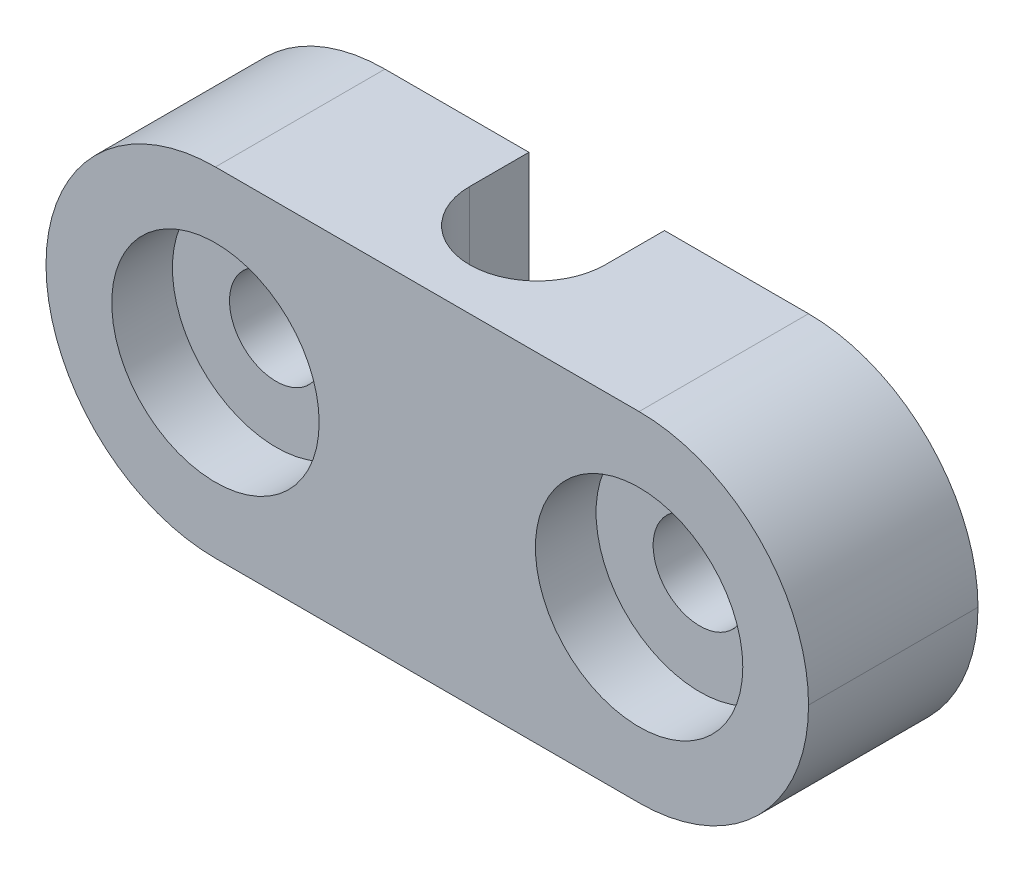
SolidWorks part; units mm, degrees
material "Plain Carbon Steel"
ref_plane "Front Plane" through (0, 0, 0) normal (0, 0, 1) x (1, 0, 0)
ref_plane "Top Plane" through (0, 0, 0) normal (0, 1, 0) x (1, 0, 0)
ref_plane "Right Plane" through (0, 0, 0) normal (1, 0, 0) x (0, 0, -1)
sketch "Sketch2" plane through (0, 0, 0) normal (0, 0, 1) x (1, 0, 0)
  line L1 (-22.5, -10) -> (22.5, -10)
  line L2 (-22.5, -10) -> (-22.5, 10)
  line L3 (-22.5, 10) -> (22.5, 10)
  line L4 (22.5, -10) -> (22.5, 10)
  line L5 (-22.5, -10) -> (22.5, 10) construction
  line L6 (-22.5, 10) -> (22.5, -10) construction
  point P0 (0, 0)
  dimension "D1" = 45
  dimension "D2" = 20
extrude "Boss-Extrude2" add sketch "Sketch2" along normal blind 10
fillet "Fillet1" radius 10 4 edges at (22.5, 10, 5) (22.5, -10, 5) (-22.5, 10, 5) (-22.5, -10, 5)
sketch "Sketch3" plane through (0, -10, 0) normal (0, -1, 0) x (1, 0, 0)
  line L0 (0, 0) -> (0, 3.5) construction
  line L1 (-12.5, 0) -> (12.5, 0) construction
  line L2 (-4, 0) -> (-4, 3.5)
  line L3 (4, 0) -> (4, 3.5)
  line L5 (-12.5, 10) -> (12.5, 10) construction
  arc A0 (-4, 0) -> (4, 0) centre (0, 0) ccw
  arc A1 (4, 3.5) -> (-4, 3.5) centre (0, 3.5) ccw
  point P4 (0, 1.75)
  dimension "D2" = 7.5
  dimension "D3" = 2.5
  dimension "D1" = 8
extrude "Cut-Extrude1" cut sketch "Sketch3" against normal blind 22
hole_wizard "CBORE for M5 Hex Head Bolt1" positions "Sketch8" profile "Sketch7" counterbore size "M5" standard "ANSI Metric" end condition through all
sketch "Sketch8" plane through (0, 0, 10) normal (0, 0, 1) x (1, 0, 0)
  point P0 (-12.5, 0)
  point P2 (12.5, 0)
  dimension "D1" = 25
  dimension "D2" = 10
  dimension "D3" = 10
sketch "Sketch7" plane through (-12.5, 0, 10) normal (1, 0, 0) x (0, -1, 0)
  line L0 (0, 0) -> (0, 10)
  line L1 (0, 10) -> (2.75, 10)
  line L3 (2.75, 10) -> (2.75, 3.58)
  line L4 (2.75, 3.58) -> (6.12, 3.58)
  line L5 (6.12, 3.58) -> (6.12, 0)
  line L7 (6.12, 0) -> (0, 0)
  line L11 (0, -6.35) -> (0, 107.95) construction
  dimension "Thru Hole Dia." = 5.5
  dimension "Thru Hole Depth" = 10
  dimension "C'Bore Dia." = 12.24
  dimension "C'Bore Depth" = 3.58
